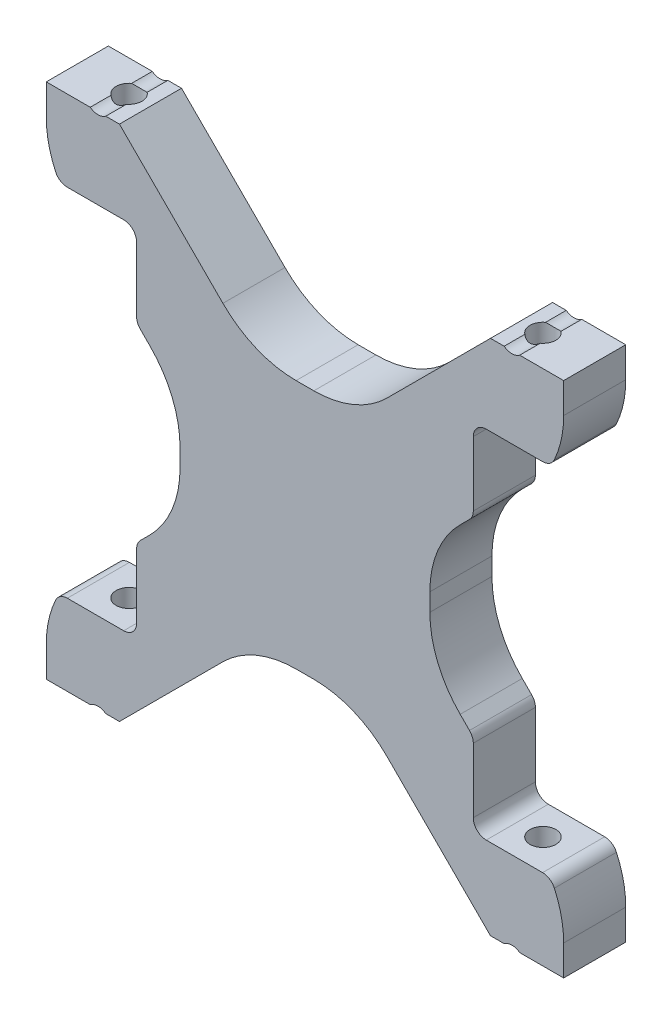
SolidWorks part; units mm, degrees
ref_plane "正面" through (0, 0, 0) normal (0, 0, 1) x (1, 0, 0)
ref_plane "平面" through (0, 0, 0) normal (0, 1, 0) x (1, 0, 0)
ref_plane "右側面" through (0, 0, 0) normal (1, 0, 0) x (0, 0, -1)
sketch "ｽｹｯﾁ1" plane through (0, 0, 0) normal (0, 0, 1) x (1, 0, 0)
  line L0 (-32.0711, 25) -> (-12.0711, 5)
  line L1 (-12.0711, -5) -> (-32.0711, -25)
  line L2 (-32.0711, -25) -> (-17.9289, -25)
  line L3 (-17.9289, -25) -> (-5, -12.0711)
  line L4 (5, -12.0711) -> (17.9289, -25)
  line L5 (17.9289, -25) -> (32.0711, -25)
  line L6 (32.0711, -25) -> (12.0711, -5)
  line L7 (12.0711, 5) -> (32.0711, 25)
  line L8 (32.0711, 25) -> (17.9289, 25)
  line L9 (17.9289, 25) -> (5, 12.0711)
  line L10 (-5, 12.0711) -> (-17.9289, 25)
  line L11 (-17.9289, 25) -> (-32.0711, 25)
  line L12 (-12.0711, 5) -> (-12.0711, -5)
  line L13 (-5, -12.0711) -> (5, -12.0711)
  line L14 (12.0711, -5) -> (12.0711, 5)
  line L15 (5, 12.0711) -> (-5, 12.0711)
  line L16 (12.0711, 5) -> (-12.0711, -5) construction
  line L17 (-12.0711, 5) -> (12.0711, -5) construction
  line L18 (-12.0711, 5) -> (12.0711, 5) construction
  line L19 (5, 12.0711) -> (-5, -12.0711) construction
  line L20 (-5, 12.0711) -> (5, -12.0711) construction
  point P1 (0, 0)
  point P11 (0, 0)
  dimension "D1" = 10
  dimension "D2" = 135
  dimension "D3" = 10
  dimension "D4" = 10
  dimension "D5" = 50
  dimension "D6" = 135
extrude "ﾎﾞｽ - 押し出し1" add sketch "ｽｹｯﾁ1" along normal blind 6
sketch "ｽｹｯﾁ2" plane through (0, 0, 6) normal (0, 0, 1) x (1, 0, 0)
  line L0 (0, 0) -> (0, 38.1314) construction
  line L1 (-17.9289, 25) -> (-32.0711, 25) construction
  line L2 (-20.75, 25) -> (-19.25, 25)
  line L3 (20.75, 25) -> (19.25, 25)
  arc A0 (-20.75, 25) -> (-19.25, 25) centre (-20, 26) ccw
  arc A1 (20.75, 25) -> (19.25, 25) centre (20, 26) cw
  dimension "D1" = 20
  dimension "D2" = 2.5
  dimension "D3" = 1
extrude "ｶｯﾄ - 押し出し1" cut sketch "ｽｹｯﾁ2" against normal through all
fillet "ﾌｨﾚｯﾄ1" radius 2 2 edges at (32.0711, 25, 3) (-32.0711, 25, 3)
ref_plane "平面1" through (0, 0, 0) normal (0, 1, 0) x (1, 0, 0)
mirror "ﾐﾗｰ3" about plane through (0, 0, 0) normal (0, 1, 0) of "ｶｯﾄ - 押し出し1", "ﾌｨﾚｯﾄ1"
sketch "ｽｹｯﾁ3" plane through (0, 25, 0) normal (0, 1, 0) x (1, 0, 0)
  line L0 (-29.2426, -3) -> (29.2426, -3) construction
  line L1 (-29.2426, 0) -> (-29.2426, -6) construction
  line L2 (29.2426, -6) -> (29.2426, 0) construction
  line L3 (-20, 0) -> (-20, -6) construction
  line L4 (-19.25, 0) -> (-20.75, 0) construction
  line L5 (-20.75, -6) -> (-19.25, -6) construction
  line L6 (20, 0) -> (20, -6) construction
  line L7 (20.75, 0) -> (19.25, 0) construction
  line L8 (19.25, -6) -> (20.75, -6) construction
  circle A0 centre (-20, -3) radius 1.25
  circle A1 centre (20, -3) radius 1.25
  dimension "D1" = 2.5
extrude "ｶｯﾄ - 押し出し2" cut sketch "ｽｹｯﾁ3" against normal through all
sketch "ｽｹｯﾁ4" plane through (0, 0, 6) normal (0, 0, 1) x (1, 0, 0)
  line L0 (27.2426, 25) -> (20.75, 25) construction
  line L2 (-25, -25) -> (-25, 25)
  line L4 (25, -25) -> (25, 25)
  line L5 (-25, -25) -> (25, 25) construction
  line L6 (-25, 25) -> (25, -25) construction
  line L7 (-27.2426, -25) -> (-20.75, -25) construction
  line L8 (29.2426, 25) -> (25, 25)
  line L9 (29.2426, 25) -> (29.2426, -25)
  line L10 (29.2426, -25) -> (25, -25)
  line L11 (-29.2426, 25) -> (-29.2426, -25)
  line L12 (29.2426, 25) -> (-29.2426, -25) construction
  line L13 (29.2426, -25) -> (-29.2426, 25) construction
  line L14 (-25, -25) -> (-29.2426, -25)
  line L15 (-25, 25) -> (-29.2426, 25)
  arc A0 (-28.6569, -21.5858) -> (-27.2426, -25) centre (-27.2426, -23) ccw construction
  point P0 (0, 0)
  point P8 (0, 0)
extrude "ｶｯﾄ - 押し出し3" cut sketch "ｽｹｯﾁ4" against normal through all
fillet "ﾌｨﾚｯﾄ2" radius 10 12 edges at (25, 17.9289, 3) (12.0711, 5, 3) (12.0711, -5, 3) (25, -17.9289, 3) (5, -12.0711, 3) (-5, -12.0711, 3) (-25, -17.9289, 3) (-12.0711, -5, 3) (-12.0711, 5, 3) (-25, 17.9289, 3) (5, 12.0711, 3) (-5, 12.0711, 3)
sketch "ｽｹｯﾁ5" plane through (0, 0, 6) normal (0, 0, 1) x (1, 0, 0)
  line L0 (-20, 26) -> (-20, 12.9289) construction
  line L1 (-22.0711, 15) -> (-15, 7.9289) construction
  line L2 (0, 12.0711) -> (0, -12.0711) construction
  line L3 (-23.7318, 17.1971) -> (-16.2682, 17.1971)
  line L4 (-23.7318, 17.1971) -> (-23.7318, 9.1971)
  line L5 (-23.7318, 9.1971) -> (-16.2682, 9.1971)
  line L6 (-16.2682, 17.1971) -> (-16.2682, 9.1971)
  line L7 (-23.7318, 17.1971) -> (-16.2682, 9.1971) construction
  line L8 (-23.7318, 9.1971) -> (-16.2682, 17.1971) construction
  line L9 (0.8579, 12.0711) -> (-0.8579, 12.0711) construction
  line L10 (-0.8579, -12.0711) -> (0.8579, -12.0711) construction
  line L11 (-12.0711, 0) -> (12.0711, 0) construction
  line L12 (-12.0711, 0.8579) -> (-12.0711, -0.8579) construction
  line L13 (12.0711, -0.8579) -> (12.0711, 0.8579) construction
  line L14 (23.7318, 9.1971) -> (16.2682, 9.1971)
  line L15 (16.2682, 17.1971) -> (16.2682, 9.1971)
  line L16 (23.7318, 17.1971) -> (16.2682, 17.1971)
  line L17 (23.7318, 17.1971) -> (23.7318, 9.1971)
  line L18 (-23.7318, -9.1971) -> (-16.2682, -9.1971)
  line L19 (-16.2682, -17.1971) -> (-16.2682, -9.1971)
  line L20 (-23.7318, -17.1971) -> (-16.2682, -17.1971)
  line L21 (-23.7318, -17.1971) -> (-23.7318, -9.1971)
  line L22 (23.7318, -17.1971) -> (23.7318, -9.1971)
  line L23 (23.7318, -17.1971) -> (16.2682, -17.1971)
  line L24 (16.2682, -17.1971) -> (16.2682, -9.1971)
  line L25 (23.7318, -9.1971) -> (16.2682, -9.1971)
  arc A0 (-25, 22.0711) -> (-22.0711, 15) centre (-15, 22.0711) ccw construction
  point P5 (-20, 13.1971)
  dimension "D1" = 8
extrude "ｶｯﾄ - 押し出し4" cut sketch "ｽｹｯﾁ5" against normal through all
fillet "ﾌｨﾚｯﾄ3" radius 1.25 12 edges at (-23.7318, -17.1971, 3) (-16.2682, -17.1971, 3) (-16.2682, -9.1971, 3) (23.7318, -17.1971, 3) (16.2682, -9.1971, 3) (16.2682, -17.1971, 3) (16.2682, 9.1971, 3) (23.7318, 17.1971, 3) (16.2682, 17.1971, 3) (-16.2682, 9.1971, 3) (-23.7318, 17.1971, 3) (-16.2682, 17.1971, 3)
